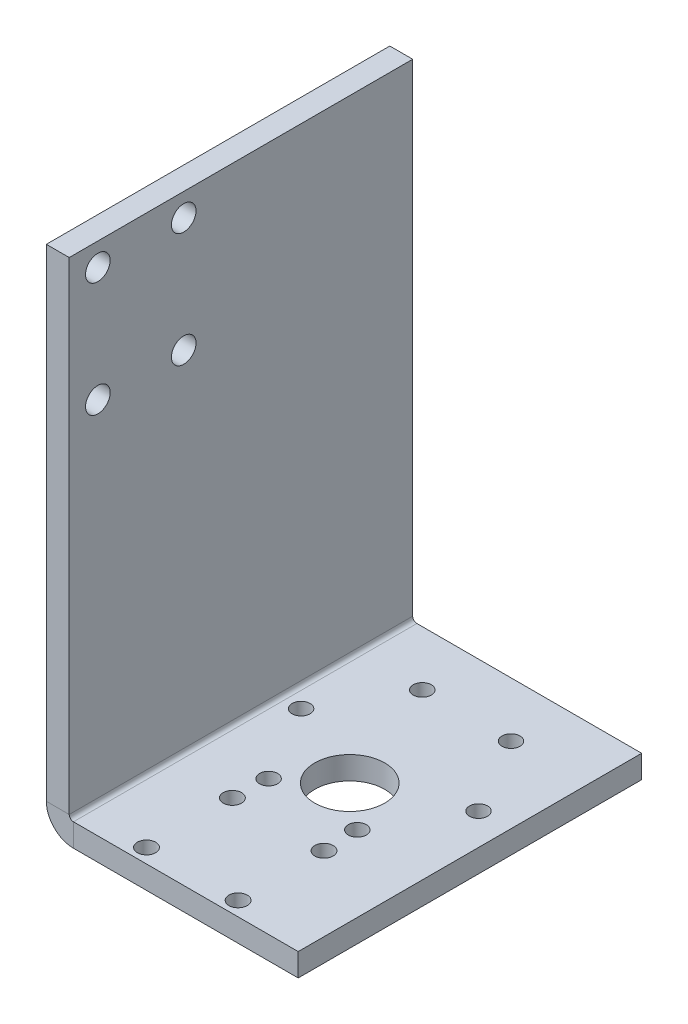
SolidWorks part; units mm, degrees
note: The reader was unsure of these and kept them because the rebuilt part matched: thickness of "基材-凸緣2", "鈑金4", "鈑金6", "鈑金7", "鈑金8", "鈑金9", "鈑金12"; bend radius of "基材彎折1".
material "AISI 304"
ref_plane "前基準面" through (0, 0, 0) normal (0, 0, 1) x (1, 0, 0)
ref_plane "上基準面" through (0, 0, 0) normal (0, 1, 0) x (1, 0, 0)
ref_plane "右基準面" through (0, 0, 0) normal (1, 0, 0) x (0, 0, -1)
sketch "草圖16" plane through (0, 0, 0) normal (0, 0, 1) x (1, 0, 0)
  line L0 (0, 0) -> (0, 85)
  line L1 (0, 0) -> (40, 0)
  dimension "D1" = 40
  dimension "D2" = 85
base flange "基材-凸緣2" sketch "草圖16" end condition mid plane depth 60 reverse direction no thickness 4 reverse thickness direction no bend radius 0.7366
bend "基材彎折1" bend radius 0.7366 bend angle 90 parameters "D5"=1
hole_wizard "M3 餘隙孔1" positions "草圖22" profile "草圖23" hole size "M3" standard "Ansi Metric" end condition through all
sketch "草圖22" plane through (0, 0, 0) normal (0, -1, 0) x (-1, 0, 0)
  line L1 (-11, -12.5) -> (-27, -12.5) construction
  line L2 (-11, -12.5) -> (-11, -27.5) construction
  line L3 (-11, -27.5) -> (-27, -27.5) construction
  line L4 (-27, -12.5) -> (-27, -27.5) construction
  line L5 (-11, -12.5) -> (-27, -27.5) construction
  line L6 (-11, -27.5) -> (-27, -12.5) construction
  line L11 (4, -30) -> (4, 30) construction
  line L13 (-0.7366, -30) -> (-40, -30) construction
  point P2 (-27, -27.5)
  point P57 (-11, -12.5)
  point P58 (-11, -27.5)
  point P59 (-27, -12.5)
  point P95 (-19, -20)
  dimension "D1" = 16
  dimension "D2" = 15
  dimension "D3" = 10
  dimension "D4" = 15
sketch "草圖23" plane through (27, 0, 27.5) normal (1, 0, 0) x (0, 0, 1)
  line L0 (0, 0) -> (0, 4)
  line L1 (0, 4) -> (1.6, 4)
  line L2 (1.6, 4) -> (1.6, 0)
  line L5 (1.6, 0) -> (0, 0)
  line L11 (0, -6.35) -> (0, 107.95) construction
  dimension "砮 ふ 畖" = 3.2
  dimension "砮 ふ瞏 " = 4
sketch "草圖24" plane through (0, -4, 0) normal (0, -1, 0) x (1, 0, 0)
  line L0 (19, 20) -> (19, 0) construction
  line L1 (11, 27.5) -> (27, 27.5) construction
  line L2 (11, 27.5) -> (11, 12.5) construction
  line L3 (11, 12.5) -> (27, 12.5) construction
  line L4 (27, 27.5) -> (27, 12.5) construction
  line L5 (11, 27.5) -> (27, 12.5) construction
  line L6 (11, 12.5) -> (27, 27.5) construction
  circle A0 centre (19, 0) radius 6.1
  point P4 (19, 20)
  point P13 (19, 0)
  dimension "D1" = 12.2
  dimension "D2" = 20
extrude "除料-伸長2" cut sketch "草圖24" against normal through all normal cut yes
hole_wizard "M4 餘隙孔1" positions "草圖27" profile "草圖28" hole size "M4" standard "Ansi Metric" end condition through all
sketch "草圖27" plane through (0, 0, 0) normal (-1, 0, 0) x (0, 0, 1)
  line L1 (25, 81) -> (-5, 81) construction
  line L2 (25, 81) -> (25, 61) construction
  line L3 (25, 61) -> (-5, 61) construction
  line L4 (-5, 81) -> (-5, 61) construction
  line L5 (25, 81) -> (-5, 61) construction
  line L6 (25, 61) -> (-5, 81) construction
  line L7 (0, 0) -> (0, 71) construction
  line L10 (30, 85) -> (-30, 85) construction
  point P104 (25, 81)
  point P105 (25, 61)
  point P133 (10, 61)
  point P135 (10, 81)
  point P137 (0, 0)
  point P138 (0, 34)
  point P139 (10, 71)
  point P140 (25, 24.0173)
  dimension "D1" = 30
  dimension "D2" = 20
  dimension "D3" = 14
  dimension "D4" = 10
sketch "草圖28" plane through (0, 81, 10) normal (0, 1, 0) x (0, 0, -1)
  line L0 (0, 0) -> (0, 4)
  line L1 (0, 4) -> (2.15, 4)
  line L2 (2.15, 4) -> (2.15, 0)
  line L5 (2.15, 0) -> (0, 0)
  line L11 (0, -6.35) -> (0, 107.95) construction
  dimension "砮 ふ 畖" = 4.3
  dimension "砮 ふ瞏 " = 4
hole_wizard "M2 餘隙孔1" positions "草圖25" profile "草圖26" hole size "M2" standard "Ansi Metric" end condition through all
sketch "草圖25" plane through (0, -4, 0) normal (0, -1, 0) x (-1, 0, 0)
  line L0 (-14, 0) -> (-24, 0) construction
  circle A0 centre (-19, 0) radius 6.1 construction
  point P0 (-14, 0)
  point P1 (-24, 0)
  point P4 (-19, 0)
  dimension "D1" = 10
sketch "草圖26" plane through (14, -4, 0) normal (1, 0, 0) x (0, 0, -1)
  line L0 (0, 0) -> (0, 89)
  line L1 (0, 89) -> (1.1, 89)
  line L2 (1.1, 89) -> (1.1, 0)
  line L5 (1.1, 0) -> (0, 0)
  line L11 (0, -6.35) -> (0, 107.95) construction
  dimension "砮 ふ 畖" = 2.2
  dimension "砮 ふ瞏 " = 89
hole_wizard "M3 螺旋的螺孔鑽1" positions "草圖29" profile "草圖31" hole size "M3x0.5" standard "Ansi Metric" end condition through all
sketch "草圖29" plane through (0, -4, 0) normal (0, -1, 0) x (-1, 0, 0)
  line L0 (-19, 0) -> (-19, 30) construction
  line L1 (-0.7366, 30) -> (-40, 30) construction
  line L5 (-3.5, 7) -> (-34.5, 7) construction
  line L8 (-11.25, -6.4234) -> (-26.75, 20.4234) construction
  line L11 (-26.75, -6.4234) -> (-11.25, 20.4234) construction
  circle A0 centre (-19, 7) radius 15.5 construction
  circle A1 centre (-19, 0) radius 6.1 construction
  point P17 (-34.5, 7)
  point P20 (-3.5, 7)
  point P22 (-11.25, -6.4234)
  point P24 (-11.25, 20.4234)
  point P26 (-26.75, 20.4234)
  point P28 (-26.75, -6.4234)
  dimension "D1" = 7
  dimension "D2" = 31
  dimension "D3" = 60
  dimension "D4" = 60
sketch "草圖31" plane through (26.75, -4, 6.4234) normal (1, 0, 0) x (0, 0, -1)
  line L0 (0, 0) -> (0, 89)
  line L1 (0, 89) -> (1.575, 89)
  line L2 (1.575, 89) -> (1.575, 0)
  line L5 (1.575, 0) -> (0, 0)
  line L11 (0, -6.35) -> (0, 107.95) construction
  dimension "貫穿孔直徑" = 3.15
  dimension "貫穿孔深度" = 89
sketch "彎折-線3" [suppressed] plane through (0, 0, 0) normal (0, 1, 0) x (1, 0, 0)
sketch "邊界方塊3" [suppressed] plane through (0, 0, 0) normal (0, 1, 0) x (1, 0, 0)
sheet metal parameters "鈑金4" thickness 4 parameters "D1"=0.7366
flat pattern "平板-型式4" [suppressed]
sketch "彎折-線4" plane through (0, 0, 0) normal (0, 1, 0) x (1, 0, 0)
  line L0 (-1.4127, -20) -> (-1.4127, 20) construction
  line L1 (-1.4127, -20) -> (-1.4127, 20) construction
sketch3d "邊界方塊4" [suppressed]
  line L0 (60, 0, 0) -> (-32.8254, 0, 0) construction
  line L1 (60, 40, 0) -> (-32.8254, 40, 0) construction
  line L2 (60, 0, 0) -> (60, 40, 0) construction
  line L3 (-32.8254, 0, 0) -> (-32.8254, 40, 0) construction
bend of the flat pattern "平板-<基材彎折1>1"
sheet metal parameters "鈑金6" thickness 4 parameters "D1"=0.7366
flat pattern "平板-型式4"
sketch "彎折-線4" plane through (0, 0, 0) normal (0, 1, 0) x (1, 0, 0)
  line L0 (-1.4127, -20) -> (-1.4127, 20) construction
  line L1 (-1.4127, -20) -> (-1.4127, 20) construction
sketch3d "邊界方塊4" [suppressed]
  line L0 (40, 0, 0) -> (-42.8254, 0, 0) construction
  line L1 (40, 40, 0) -> (-42.8254, 40, 0) construction
  line L2 (40, 0, 0) -> (40, 40, 0) construction
  line L3 (-42.8254, 0, 0) -> (-42.8254, 40, 0) construction
bend of the flat pattern "平板-<基材彎折1>1"
sheet metal parameters "鈑金7" thickness 4 parameters "D1"=0.7366
flat pattern "平板-型式4"
sketch "彎折-線4" plane through (0, 0, 0) normal (0, 1, 0) x (1, 0, 0)
  line L0 (-1.4127, -20) -> (-1.4127, 20) construction
  line L1 (-1.4127, -20) -> (-1.4127, 20) construction
sketch3d "邊界方塊4" [suppressed]
  line L0 (40, 0, 0) -> (-42.8254, 0, 0) construction
  line L1 (40, 40, 0) -> (-42.8254, 40, 0) construction
  line L2 (40, 0, 0) -> (40, 40, 0) construction
  line L3 (-42.8254, 0, 0) -> (-42.8254, 40, 0) construction
bend of the flat pattern "平板-<基材彎折1>1"
sheet metal parameters "鈑金8" thickness 4 parameters "D1"=0.7366
flat pattern "平板-型式4"
sketch "彎折-線4" plane through (0, 0, 0) normal (0, 1, 0) x (1, 0, 0)
  line L0 (-1.4127, -30) -> (-1.4127, 30) construction
  line L1 (-1.4127, -30) -> (-1.4127, 30) construction
sketch3d "邊界方塊4" [suppressed]
  line L0 (36, 0, 0) -> (-50.8254, 0, 0) construction
  line L1 (36, 60, 0) -> (-50.8254, 60, 0) construction
  line L2 (36, 0, 0) -> (36, 60, 0) construction
  line L3 (-50.8254, 0, 0) -> (-50.8254, 60, 0) construction
bend of the flat pattern "平板-<基材彎折1>1"
sheet metal parameters "鈑金9" thickness 4 parameters "D1"=0.7366
flat pattern "平板-型式4"
sketch "彎折-線4" plane through (0, 0, 0) normal (0, 1, 0) x (1, 0, 0)
  line L0 (-1.02, -30) -> (-1.02, 30) construction
  line L1 (-1.02, -30) -> (-1.02, 30) construction
sketch3d "邊界方塊4" [suppressed]
  line L0 (40, 0, 0) -> (-52.04, 0, 0) construction
  line L1 (40, 60, 0) -> (-52.04, 60, 0) construction
  line L2 (40, 0, 0) -> (40, 60, 0) construction
  line L3 (-52.04, 0, 0) -> (-52.04, 60, 0) construction
bend of the flat pattern "平板-<基材彎折1>1"
sheet metal parameters "鈑金12" thickness 4 parameters "D1"=0.7366
flat pattern "平板-型式4"
sketch "彎折-線4" plane through (0, 0, 0) normal (0, 1, 0) x (1, 0, 0)
  line L0 (-1.4127, -30) -> (-1.4127, 30) construction
  line L1 (-1.4127, -30) -> (-1.4127, 30) construction
sketch3d "邊界方塊4" [suppressed]
  line L0 (40, 0, 0) -> (-87.8254, 0, 0) construction
  line L1 (40, 60, 0) -> (-87.8254, 60, 0) construction
  line L2 (40, 0, 0) -> (40, 60, 0) construction
  line L3 (-87.8254, 0, 0) -> (-87.8254, 60, 0) construction
bend of the flat pattern "平板-<基材彎折1>1"
